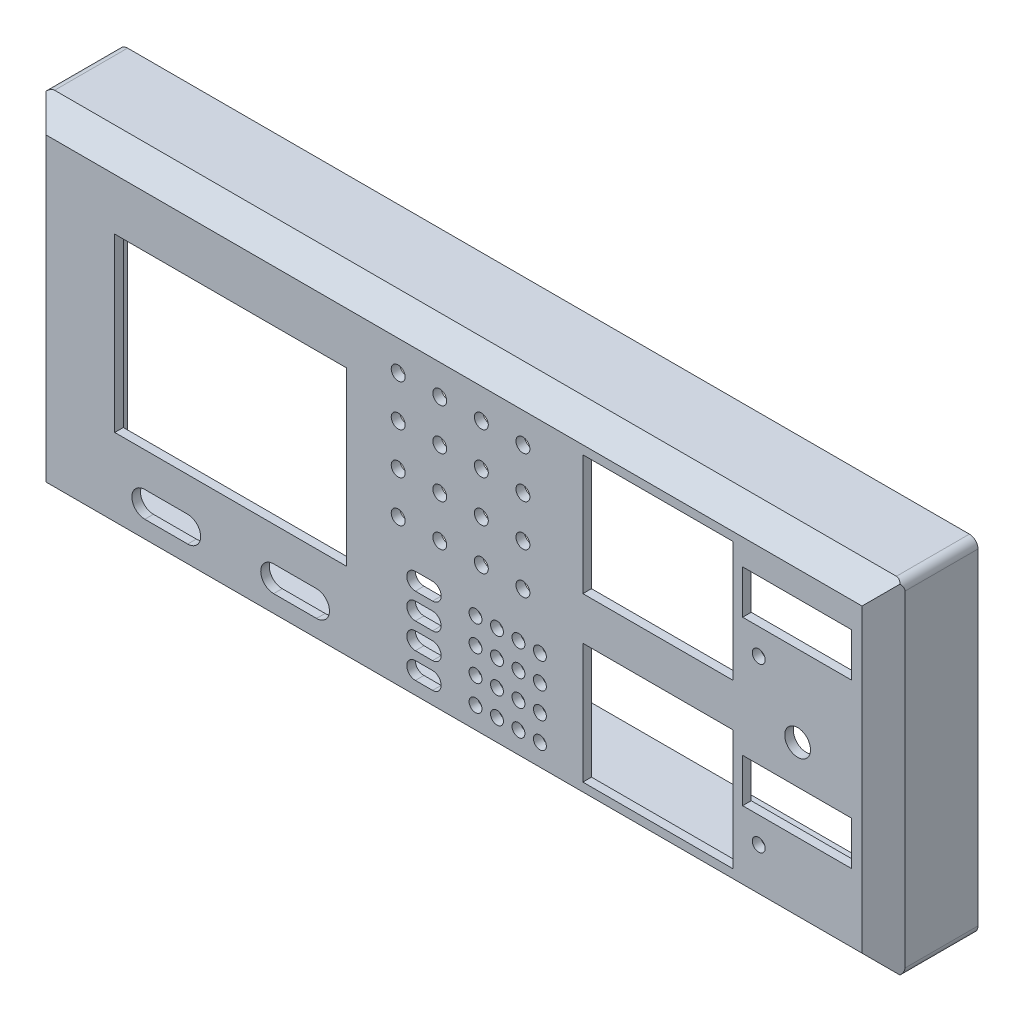
SolidWorks part; units mm, degrees
ref_plane "Front Plane" through (0, 0, 0) normal (0, 0, 1) x (1, 0, 0)
ref_plane "Top Plane" through (0, 0, 0) normal (0, 1, 0) x (1, 0, 0)
ref_plane "Right Plane" through (0, 0, 0) normal (1, 0, 0) x (0, 0, -1)
sketch "Sketch1" plane through (0, 0, 0) normal (0, 0, 1) x (1, 0, 0)
  line L0 (70.5501, 42.5931) -> (10.544, 42.5931) construction
  line L1 (194.7438, -17.4069) -> (-5.2562, -17.4069)
  line L2 (194.7438, -17.4069) -> (194.7438, 62.5931)
  line L3 (194.7438, 62.5931) -> (-5.2562, 62.5931)
  line L4 (-5.2562, -17.4069) -> (-5.2562, 62.5931)
  line L5 (194.7438, -17.4069) -> (-5.2562, 62.5931) construction
  line L6 (194.7438, 62.5931) -> (-5.2562, -17.4069) construction
  line L7 (14.7438, 31.8244) -> (14.7438, 0.0127) construction
  point P0 (94.7438, 22.5931)
  dimension "D1" = 80
  dimension "D2" = 200
  dimension "D3" = 20
  dimension "D4" = 20
extrude "Boss-Extrude1" add sketch "Sketch1" along normal blind 2 and the other way blind 20
chamfer "Chamfer1" distance 5 angle 45 4 edges at (194.7438, 22.5931, 2) (94.7438, -17.4069, 2) (-5.2562, 22.5931, 2) (94.7438, 62.5931, 2)
fillet "Fillet1" radius 2 4 edges at (194.7438, -17.4069, -11.5) (-5.2562, -17.4069, -11.5) (194.7438, 62.5931, -11.5) (-5.2562, 62.5931, -11.5)
shell "Shell1" thickness 2 removed face at (94.7438, 22.5931, -20)
sketch "Sketch2" plane through (0, 0, 2) normal (0, 0, 1) x (1, 0, 0)
  line L0 (-5.2562, -17.4069) -> (-5.2562, 62.5931) construction
  line L1 (15.7438, 5.5931) -> (69.7438, 5.5931)
  line L2 (15.7438, 5.5931) -> (15.7438, 45.5931)
  line L3 (15.7438, 45.5931) -> (69.7438, 45.5931)
  line L4 (69.7438, 5.5931) -> (69.7438, 45.5931)
  line L5 (15.7438, 5.5931) -> (69.7438, 45.5931) construction
  line L6 (15.7438, 45.5931) -> (69.7438, 5.5931) construction
  line L7 (194.7438, 62.5931) -> (-5.2562, 62.5931) construction
  point P0 (42.7438, 25.5931)
  dimension "D1" = 54
  dimension "D2" = 40
  dimension "D3" = 21
  dimension "D4" = 17
extrude "Cut-Extrude1" cut sketch "Sketch2" against normal blind 2
sketch "Sketch4" plane through (0, 0, 2) normal (0, 0, 1) x (1, 0, 0)
  line L0 (69.7438, 5.5931) -> (69.7438, 45.5931) construction
  line L1 (194.7438, -17.4069) -> (-5.2562, -17.4069) construction
  circle A0 centre (99.7438, -7.4069) radius 1.5
  circle A1 centre (104.7438, -7.4069) radius 1.5
  circle A2 centre (109.7438, -7.4069) radius 1.5
  circle A3 centre (114.7438, -7.4069) radius 1.5
  circle A4 centre (104.7438, -1.4069) radius 1.5
  circle A5 centre (109.7438, -1.4069) radius 1.5
  circle A6 centre (114.7438, -1.4069) radius 1.5
  circle A7 centre (104.7438, 4.5931) radius 1.5
  circle A8 centre (109.7438, 4.5931) radius 1.5
  circle A9 centre (114.7438, 4.5931) radius 1.5
  circle A10 centre (104.7438, 10.5931) radius 1.5
  circle A11 centre (109.7438, 10.5931) radius 1.5
  circle A12 centre (114.7438, 10.5931) radius 1.5
  circle A13 centre (99.7438, -1.4069) radius 1.5
  circle A14 centre (99.7438, 4.5931) radius 1.5
  circle A15 centre (99.7438, 10.5931) radius 1.5
  dimension "D1" = 3
  dimension "D2" = 30
  dimension "D3" = 10
  dimension "D4" = 4
  dimension "D5" = 4
extrude "Cut-Extrude2" cut sketch "Sketch4" against normal blind 2
sketch "Sketch7" plane through (0, 0, 2) normal (0, 0, 1) x (1, 0, 0)
  line L0 (85.7438, 10.5931) -> (89.7438, 10.5931) construction
  line L1 (85.7438, 12.5931) -> (89.7438, 12.5931)
  line L2 (85.7438, 8.5931) -> (89.7438, 8.5931)
  line L3 (69.7438, 5.5931) -> (69.7438, 45.5931) construction
  line L8 (85.7438, 4.5931) -> (89.7438, 4.5931) construction
  line L11 (85.7438, 6.5931) -> (89.7438, 6.5931)
  line L14 (85.7438, 2.5931) -> (89.7438, 2.5931)
  line L15 (85.7438, -1.4069) -> (89.7438, -1.4069) construction
  line L16 (85.7438, 0.5931) -> (89.7438, 0.5931)
  line L17 (85.7438, -3.4069) -> (89.7438, -3.4069)
  line L18 (85.7438, -7.4069) -> (89.7438, -7.4069) construction
  line L19 (85.7438, -5.4069) -> (89.7438, -5.4069)
  line L20 (85.7438, -9.4069) -> (89.7438, -9.4069)
  arc A0 (85.7438, 12.5931) -> (85.7438, 8.5931) centre (85.7438, 10.5931) ccw
  arc A1 (89.7438, 8.5931) -> (89.7438, 12.5931) centre (89.7438, 10.5931) ccw
  circle A2 centre (99.7438, 10.5931) radius 1.5 construction
  arc A11 (85.7438, 6.5931) -> (85.7438, 2.5931) centre (85.7438, 4.5931) ccw
  arc A12 (89.7438, 2.5931) -> (89.7438, 6.5931) centre (89.7438, 4.5931) ccw
  arc A13 (85.7438, 0.5931) -> (85.7438, -3.4069) centre (85.7438, -1.4069) ccw
  arc A14 (89.7438, -3.4069) -> (89.7438, 0.5931) centre (89.7438, -1.4069) ccw
  arc A15 (85.7438, -5.4069) -> (85.7438, -9.4069) centre (85.7438, -7.4069) ccw
  arc A16 (89.7438, -9.4069) -> (89.7438, -5.4069) centre (89.7438, -7.4069) ccw
  point P2 (87.7438, 10.5931)
  point P15 (87.7438, 4.5931)
  point P22 (87.7438, -1.4069)
  point P29 (87.7438, -7.4069)
  dimension "D1" = 4
  dimension "D2" = 4
  dimension "D3" = 18
  dimension "D4" = 0
  dimension "D5" = 4
extrude "Cut-Extrude3" cut sketch "Sketch7" against normal blind 2
sketch "Sketch8" plane through (0, 0, 2) normal (0, 0, 1) x (1, 0, 0)
  line L0 (189.7438, 57.5931) -> (-0.2562, 57.5931) construction
  line L1 (124.7438, 27.5931) -> (159.7438, 27.5931)
  line L2 (124.7438, 27.5931) -> (124.7438, 55.5931)
  line L3 (124.7438, 55.5931) -> (159.7438, 55.5931)
  line L4 (159.7438, 27.5931) -> (159.7438, 55.5931)
  line L5 (124.7438, 27.5931) -> (159.7438, 55.5931) construction
  line L6 (124.7438, 55.5931) -> (159.7438, 27.5931) construction
  line L7 (189.7438, -12.4069) -> (189.7438, 57.5931) construction
  line L8 (124.7438, -10.4069) -> (124.7438, 17.5931)
  line L9 (124.7438, -10.4069) -> (159.7438, -10.4069)
  line L10 (159.7438, -10.4069) -> (159.7438, 17.5931)
  line L11 (124.7438, 17.5931) -> (159.7438, 17.5931)
  point P0 (142.2438, 41.5931)
  dimension "D1" = 35
  dimension "D2" = 28
  dimension "D3" = 2
  dimension "D4" = 30
extrude "Cut-Extrude4" cut sketch "Sketch8" against normal blind 2
sketch "Sketch9" plane through (0, 0, 2) normal (0, 0, 1) x (1, 0, 0)
  line L1 (161.9438, 41.4331) -> (187.3438, 41.4331)
  line L2 (161.9438, 41.4331) -> (161.9438, 51.5931)
  line L3 (161.9438, 51.5931) -> (187.3438, 51.5931)
  line L4 (187.3438, 41.4331) -> (187.3438, 51.5931)
  line L5 (161.9438, 41.4331) -> (187.3438, 51.5931) construction
  line L6 (161.9438, 51.5931) -> (187.3438, 41.4331) construction
  line L7 (161.9438, 3.4331) -> (187.3438, 3.4331)
  line L8 (161.9438, 3.4331) -> (161.9438, 13.5931)
  line L9 (161.9438, 13.5931) -> (187.3438, 13.5931)
  line L10 (187.3438, 3.4331) -> (187.3438, 13.5931)
  line L11 (161.9438, 3.4331) -> (187.3438, 13.5931) construction
  line L12 (161.9438, 13.5931) -> (187.3438, 3.4331) construction
  line L14 (189.7438, -12.4069) -> (189.7438, 57.5931) construction
  line L15 (159.7438, 55.5931) -> (124.7438, 55.5931) construction
  line L16 (159.7438, 17.5931) -> (124.7438, 17.5931) construction
  point P0 (174.6438, 46.5131)
  point P5 (174.6438, 8.5131)
  dimension "D1" = 25.4
  dimension "D2" = 10.16
  dimension "D3" = 25.4
  dimension "D4" = 10.16
  dimension "D5" = 4
  dimension "D6" = 4
  dimension "D7" = 2.4
  dimension "D8" = 2.4
extrude "Cut-Extrude5" cut sketch "Sketch9" against normal blind 2
sketch "Sketch10" plane through (0, 0, 2) normal (0, 0, 1) x (1, 0, 0)
  line L0 (194.7438, -17.4069) -> (194.7438, 62.5931) construction
  line L1 (194.7438, 62.5931) -> (-5.2562, 62.5931) construction
  circle A0 centre (174.7438, 22.5931) radius 3
  dimension "D1" = 6
  dimension "D2" = 20
  dimension "D3" = 40
extrude "Cut-Extrude6" cut sketch "Sketch10" against normal blind 2
sketch "Sketch11" plane through (0, 0, 2) normal (0, 0, 1) x (1, 0, 0)
  line L0 (161.9438, 41.4331) -> (187.3438, 41.4331) construction
  line L1 (161.9438, 3.4331) -> (187.3438, 3.4331) construction
  circle A0 centre (165.686, 35.4331) radius 1.5
  circle A1 centre (165.686, -2.5669) radius 1.5
  dimension "D1" = 3
  dimension "D2" = 3
  dimension "D3" = 6
  dimension "D4" = 6
extrude "Cut-Extrude7" cut sketch "Sketch11" against normal blind 2
sketch "Sketch12" plane through (0, 0, 2) normal (0, 0, 1) x (1, 0, 0)
  line L0 (22.7438, -5.4069) -> (32.7438, -5.4069) construction
  line L1 (22.7438, -2.4069) -> (32.7438, -2.4069)
  line L2 (22.7438, -8.4069) -> (32.7438, -8.4069)
  line L3 (15.7438, 45.5931) -> (15.7438, 5.5931) construction
  line L4 (194.7438, -17.4069) -> (-5.2562, -17.4069) construction
  line L5 (52.7438, -5.4069) -> (62.7438, -5.4069) construction
  line L6 (52.7438, -2.4069) -> (62.7438, -2.4069)
  line L7 (52.7438, -8.4069) -> (62.7438, -8.4069)
  arc A0 (22.7438, -2.4069) -> (22.7438, -8.4069) centre (22.7438, -5.4069) ccw
  arc A1 (32.7438, -8.4069) -> (32.7438, -2.4069) centre (32.7438, -5.4069) ccw
  arc A2 (52.7438, -2.4069) -> (52.7438, -8.4069) centre (52.7438, -5.4069) ccw
  arc A3 (62.7438, -8.4069) -> (62.7438, -2.4069) centre (62.7438, -5.4069) ccw
  point P2 (27.7438, -5.4069)
  point P13 (57.7438, -5.4069)
  dimension "D2" = 3
  dimension "D1" = 10
  dimension "D3" = 12
  dimension "D4" = 12
extrude "Cut-Extrude8" cut sketch "Sketch12" against normal blind 2
sketch "Sketch13" plane through (0, 0, 2) normal (0, 0, 1) x (1, 0, 0)
  line L0 (69.7438, 5.5931) -> (69.7438, 45.5931) construction
  line L1 (194.7438, 62.5931) -> (-5.2562, 62.5931) construction
  circle A0 centre (81.7438, 50.5931) radius 1.62
  circle A1 centre (91.4238, 50.5931) radius 1.62
  circle A2 centre (101.1038, 50.5931) radius 1.62
  circle A3 centre (110.7838, 50.5931) radius 1.62
  circle A4 centre (91.4238, 40.9131) radius 1.62
  circle A5 centre (101.1038, 40.9131) radius 1.62
  circle A6 centre (110.7838, 40.9131) radius 1.62
  circle A7 centre (91.4238, 31.2331) radius 1.62
  circle A8 centre (101.1038, 31.2331) radius 1.62
  circle A9 centre (110.7838, 31.2331) radius 1.62
  circle A10 centre (91.4238, 21.5531) radius 1.62
  circle A11 centre (101.1038, 21.5531) radius 1.62
  circle A12 centre (110.7838, 21.5531) radius 1.62
  circle A13 centre (81.7438, 40.9131) radius 1.62
  circle A14 centre (81.7438, 31.2331) radius 1.62
  circle A15 centre (81.7438, 21.5531) radius 1.62
  dimension "D1" = 3.24
  dimension "D4" = 12
  dimension "D5" = 12
  dimension "D2" = 4
  dimension "D3" = 4
extrude "Cut-Extrude9" cut sketch "Sketch13" against normal blind 2
equation "\"WALL_THICKNESS\"=2"
equation "\"D1@Boss-Extrude1\"=\"WALL_THICKNESS\""
